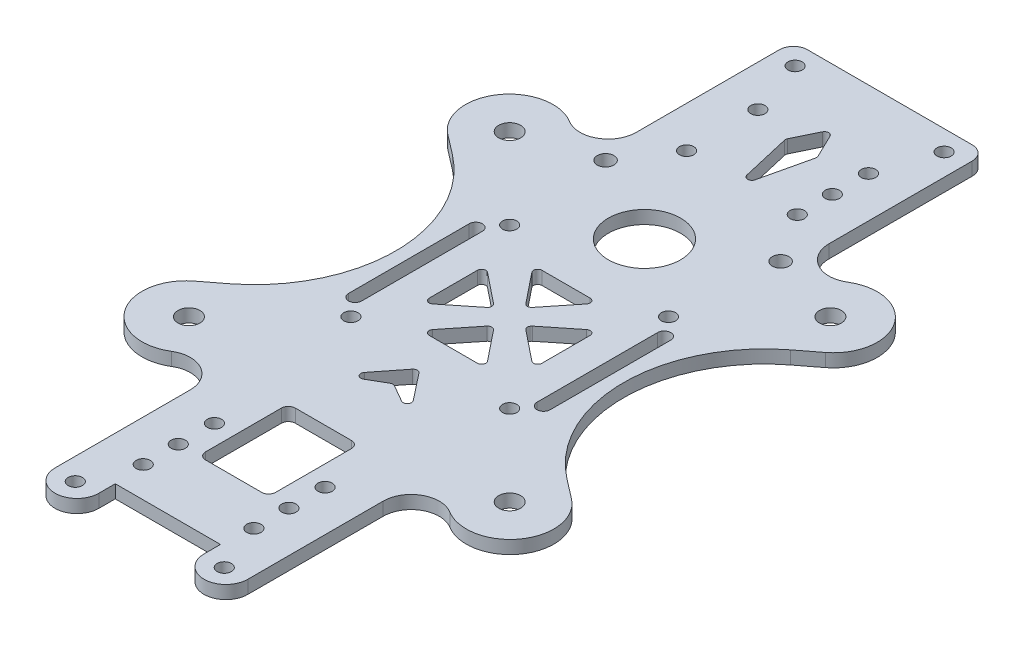
SolidWorks part; units mm, degrees
ref_plane "Front Plane" through (0, 0, 0) normal (0, 0, 1) x (1, 0, 0)
ref_plane "Top Plane" through (0, 0, 0) normal (0, 1, 0) x (1, 0, 0)
ref_plane "Right Plane" through (0, 0, 0) normal (1, 0, 0) x (0, 0, -1)
sketch "Sketch1" plane through (0, 0, 0) normal (0, 1, 0) x (1, 0, 0)
  line L0 (0, 68.8578) -> (0, -61.9125)
  line L1 (17.4625, -68.8578) -> (9.525, -68.8578)
  line L2 (17.4625, -68.8578) -> (17.4625, -30.1567)
  line L3 (17.4625, 68.8578) -> (-17.4625, 68.8578)
  line L4 (-17.4625, -68.8578) -> (-17.4625, -30.1567)
  line L5 (17.4625, -68.8578) -> (-17.4625, 68.8578) construction
  line L6 (17.4625, 68.8578) -> (-17.4625, -68.8578) construction
  line L7 (9.525, -68.8578) -> (9.525, -61.9125)
  line L8 (9.525, -61.9125) -> (-9.525, -61.9125)
  line L9 (-9.525, -68.8578) -> (-17.4625, -68.8578)
  line L10 (0, -16.2719) -> (6.8741, -25.0031)
  line L11 (-6.35, -50.0063) -> (6.35, -50.0063)
  line L12 (-6.35, -50.0063) -> (-6.35, -33.7344)
  line L13 (-6.35, -33.7344) -> (6.35, -33.7344)
  line L14 (6.35, -50.0063) -> (6.35, -33.7344)
  line L15 (-6.35, -50.0063) -> (6.35, -33.7344) construction
  line L16 (-6.35, -33.7344) -> (6.35, -50.0063) construction
  line L17 (6.8741, -25.0031) -> (0, -21.0344)
  line L18 (0, -2.7781) -> (5.9531, -10.2136)
  line L19 (5.9531, -10.2136) -> (-5.9531, -10.2136)
  line L20 (-5.9531, -10.2136) -> (0, -2.7781)
  line L30 (17.0656, 10.9234) -> (17.0656, -10.9234) construction
  line L31 (18.2563, 10.9234) -> (18.2563, -10.9234)
  line L32 (15.875, 10.9234) -> (15.875, -10.9234)
  line L33 (-55, 0) -> (55, 0) construction
  line L34 (0, 58.743) -> (2.8661, 52.8592)
  line L35 (2.8661, 52.8592) -> (0, 40.4868)
  line L36 (17.4625, 30.1567) -> (30.8194, 40.4174)
  line L37 (30.8194, 40.4174) -> (40.4903, 27.8281)
  line L38 (40.4903, 27.8281) -> (20.6375, 12.5774)
  line L39 (40.4903, -27.8281) -> (20.6375, -12.5774)
  line L40 (30.8194, -40.4174) -> (40.4903, -27.8281)
  line L41 (17.4625, -30.1567) -> (30.8194, -40.4174)
  line L42 (20.6375, 12.5774) -> (20.6375, -12.5774)
  line L43 (-17.4625, -30.1567) -> (-30.8194, -40.4174)
  line L44 (-30.8194, -40.4174) -> (-40.4903, -27.8281)
  line L45 (-40.4903, -27.8281) -> (-20.6375, -12.5774)
  line L46 (-20.6375, 12.5774) -> (-20.6375, -12.5774)
  line L47 (-40.4903, 27.8281) -> (-20.6375, 12.5774)
  line L48 (-30.8194, 40.4174) -> (-40.4903, 27.8281)
  line L49 (-17.4625, 30.1567) -> (-30.8194, 40.4174)
  line L50 (-9.525, -68.8578) -> (-9.525, -61.9125)
  line L51 (-17.0656, 10.9234) -> (-17.0656, -10.9234) construction
  line L52 (-18.2563, 10.9234) -> (-18.2563, -10.9234)
  line L53 (-15.875, 10.9234) -> (-15.875, -10.9234)
  line L54 (-2.8661, 52.8592) -> (0, 40.4868)
  line L55 (0, 58.743) -> (-2.8661, 52.8592)
  line L56 (17.4625, 30.1567) -> (17.4625, 68.8578)
  line L57 (-17.4625, 30.1567) -> (-17.4625, 68.8578)
  line L58 (-6.8741, -25.0031) -> (0, -21.0344)
  line L59 (0, -16.2719) -> (-6.8741, -25.0031)
  line L60 (14.3824, -14.3824) -> (0, 0)
  line L61 (35.6549, -34.1228) -> (30.6192, -30.2544)
  line L62 (-10.2136, 5.9531) -> (-2.7781, 0)
  line L63 (-2.7781, 0) -> (-10.2136, -5.9531)
  line L64 (-10.2136, -5.9531) -> (-10.2136, 5.9531)
  line L65 (5.9531, 10.2136) -> (0, 2.7781)
  line L66 (0, 2.7781) -> (-5.9531, 10.2136)
  line L67 (-5.9531, 10.2136) -> (5.9531, 10.2136)
  line L68 (10.2136, -5.9531) -> (2.7781, 0)
  line L69 (2.7781, 0) -> (10.2136, 5.9531)
  line L70 (10.2136, 5.9531) -> (10.2136, -5.9531)
  circle A0 centre (13.4938, -65.1867) radius 1.2898
  circle A1 centre (10.0211, -50.0063) radius 1.2898
  circle A2 centre (10.0211, -43.4578) radius 1.2898
  circle A3 centre (10.0211, -56.3563) radius 1.2898
  circle A4 centre (0, 24.4134) radius 6.5484
  circle A5 centre (10.0211, 54.9672) radius 1.2898
  circle A6 centre (10.0211, 48.4187) radius 1.2898
  circle A7 centre (10.0211, 42.0687) radius 1.2898
  arc A8 (18.2563, 10.9234) -> (15.875, 10.9234) centre (17.0656, 10.9234) ccw
  arc A9 (15.875, -10.9234) -> (18.2563, -10.9234) centre (17.0656, -10.9234) ccw
  circle A10 centre (14.3824, -14.3824) radius 1.2898
  circle A11 centre (14.3824, 14.3824) radius 1.2898
  circle A13 centre (13.4938, 65.1867) radius 1.2898
  circle A14 centre (-13.4937, -65.1867) radius 1.2898
  circle A15 centre (-10.0211, -56.3562) radius 1.2898
  circle A16 centre (-10.0211, -50.0062) radius 1.2898
  circle A17 centre (-10.0211, -43.4578) radius 1.2898
  circle A18 centre (-14.3824, -14.3824) radius 1.2898
  arc A19 (-18.2563, 10.9234) -> (-15.875, 10.9234) centre (-17.0656, 10.9234) cw
  arc A20 (-15.875, -10.9234) -> (-18.2563, -10.9234) centre (-17.0656, -10.9234) cw
  circle A21 centre (-14.3824, 14.3824) radius 1.2898
  circle A23 centre (-10.0211, 42.0688) radius 1.2898
  circle A24 centre (-10.0211, 54.9672) radius 1.2898
  circle A25 centre (-13.4938, 65.1867) radius 1.2898
  circle A26 centre (29.0455, -29.0455) radius 1.9844
  circle A27 centre (-29.0455, -29.0455) radius 1.9844
  circle A28 centre (-29.0455, 29.0455) radius 1.9844
  circle A29 centre (29.0455, 29.0455) radius 1.9844
  circle A30 centre (15.8533, 33.2239) radius 1.504
  circle A31 centre (-15.8533, 33.2239) radius 1.504
  point P0 (0, 0)
  point P10 (9.525, -65.3852)
  point P17 (13.4938, -68.8578)
  point P18 (0, -41.8703)
  point P26 (17.0656, 0)
  point P88 (0, -61.9125)
  point P100 (-17.0656, 0)
  point P111 (-10.0211, 48.4188)
  point P123 (0, 0)
  point P132 (0, 0)
  dimension "D4" = 2.5797
  dimension "D5" = 2.3813
  dimension "D11" = 10.3187
  dimension "D12" = 2.5797
  dimension "D13" = 2.5797
  dimension "D14" = 13.0969
  dimension "D23" = 3.0079
  dimension "D25" = 3.9688
  dimension "D27" = 1.1906
  dimension "D28" = 24.228
  dimension "D30" = 19.05
  dimension "D40" = 3.9688
  dimension "D42" = 17.4625
  dimension "D1" = 137.7156
  dimension "D2" = 34.925
  dimension "D3" = 7.9375
  dimension "D6" = 6.9453
  dimension "D7" = 16.2719
  dimension "D8" = 12.7
  dimension "D9" = 11.9062
  dimension "D10" = 2.3813
  dimension "D15" = 12.7
  dimension "D16" = 7.9375
  dimension "D17" = 11.1125
  dimension "D18" = 4.7625
  dimension "D19" = 9.525
  dimension "D20" = 11.9062
  dimension "D21" = 2.7781
  dimension "D32" = 9.525
  dimension "D33" = 18.2562
  dimension "D34" = 12.7
  dimension "D35" = 6.5448
  dimension "D36" = 15.875
  dimension "D37" = 41.275
  dimension "D38" = 2.3813
  dimension "D39" = 45
  dimension "D41" = 6.35
  dimension "D24" = 2
  dimension "D43" = 4
  dimension "D22" = 4
extrude "Boss-Extrude1" add sketch "Sketch1" along normal mid plane 2.3813 contours A4 L0 L54 L55 L3 L57 L49 L48 L47 L46 L45 L44 L43 L4 L9 L50 L8 L11 L12 L13 L19 L20 L63 L64 A25 A23 A21 A17 A15 A14 A16 | A4 L0 L64 L62 L18 L19 L10 L17 L13 L14 L11 L8 L7 L1 L2 L41 L40 L39 L42 L38 L37 L36 L56 L3 L34 L35 L66 L67 L65 A0 A1 A2 A3 A5 A6 region at (14.1469, 0, -2.1535) region at (-14.1389, 0, -2.243)
fillet "Fillet1" 2 edges at (-17.4625, 0, 68.8578) (-9.525, 0, 68.8578) type full round first side face at (-17.4625, 0, 49.5073) second side face at (-9.525, 0, 65.3852) middle face at (-13.4937, 0, 68.8578)
fillet "Fillet2" 2 edges at (9.525, 0, 68.8578) (17.4625, 0, 68.8578) type full round first side face at (9.525, 0, 65.3852) second side face at (17.4625, 0, 49.5073) middle face at (13.4938, 0, 68.8578)
fillet "Fillet3" 2 edges at (30.8194, 0, -40.4174) (40.4903, 0, -27.8281) type full round first side face at (24.1409, 0, -35.287) second side face at (30.5639, 0, -20.2028) middle face at (35.6549, 0, -34.1228)
fillet "Fillet4" 2 edges at (30.8194, 0, 40.4174) (40.4903, 0, 27.8281) type full round first side face at (24.1409, 0, 35.287) second side face at (30.5639, 0, 20.2028) middle face at (35.6549, 0, 34.1228)
fillet "Fillet5" 2 edges at (-40.4903, 0, 27.8281) (-30.8194, 0, 40.4174) type full round first side face at (-30.5639, 0, 20.2028) second side face at (-24.1409, 0, 35.287) middle face at (-35.6549, 0, 34.1228)
fillet "Fillet6" 2 edges at (-30.8194, 0, -40.4174) (-40.4903, 0, -27.8281) type full round first side face at (-24.1409, 0, -35.287) second side face at (-30.5639, 0, -20.2028) middle face at (-35.6549, 0, -34.1228)
fillet "Fillet9" radius 5.08 4 edges at (-17.4625, 0, -30.1567) (17.4625, 0, 30.1567) (-17.4625, 0, 30.1567) (17.4625, 0, -30.1567)
fillet "Fillet10" radius 2.54 2 edges at (17.4625, 0, -68.8578) (-17.4625, 0, -68.8578)
fillet "Fillet11" radius 0.762 20 edges at (0, 0, -40.4868) (2.8661, 0, -52.8592) (-2.8661, 0, -52.8592) (0, 0, -58.743) (6.8741, 0, 25.0031) (0, 0, 21.0344) (-6.8741, 0, 25.0031) (0, 0, 16.2719) (-5.9531, 0, 10.2136) (0, 0, 2.7781) (5.9531, 0, 10.2136) (5.9531, 0, -10.2136) (0, 0, -2.7781) (-5.9531, 0, -10.2136) (-2.7781, 0, 0) (-10.2136, 0, -5.9531) (-10.2136, 0, 5.9531) (10.2136, 0, 5.9531) (2.7781, 0, 0) (10.2136, 0, -5.9531)
fillet "Fillet14" radius 1.27 4 edges at (6.35, 0, 33.7344) (6.35, 0, 50.0063) (-6.35, 0, 33.7344) (-6.35, 0, 50.0063)
fillet "Fillet16" 2 edges at (20.6375, 0, 12.5774) (20.6375, 0, -12.5774) type full round first side face at (27.4166, 0, 17.785) second side face at (27.4166, 0, -17.785) middle face at (20.6375, 0, 0)
fillet "Fillet17" 2 edges at (-20.6375, 0, 12.5774) (-20.6375, 0, -12.5774) type full round first side face at (-27.4166, 0, 17.785) second side face at (-27.4166, 0, -17.785) middle face at (-20.6375, 0, 0)
